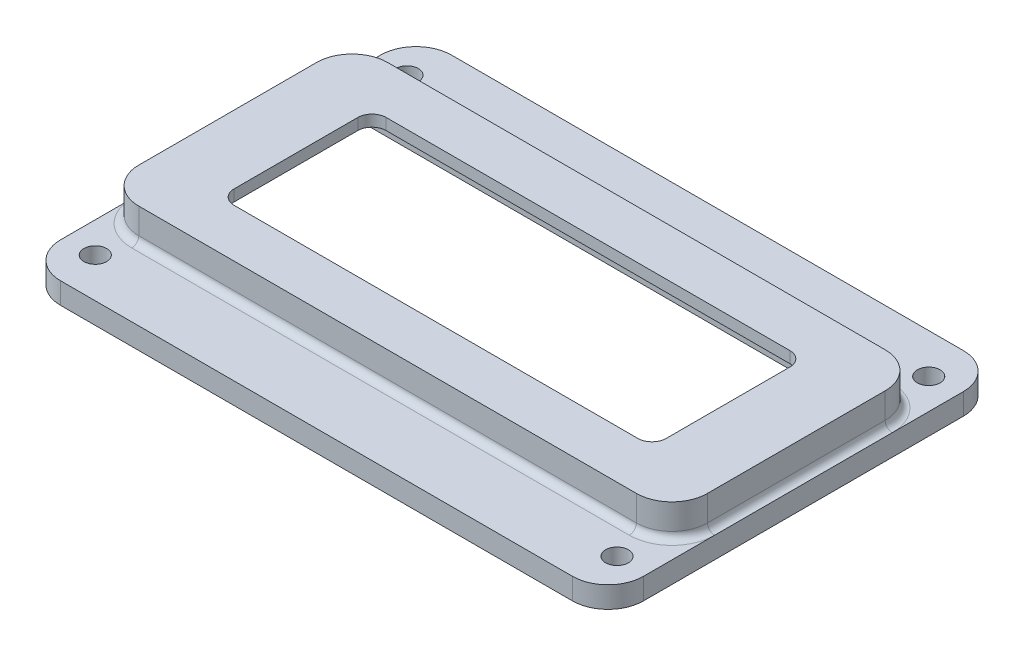
SolidWorks part; units mm, degrees
ref_plane "Front Plane" through (0, 0, 0) normal (0, 0, 1) x (1, 0, 0)
ref_plane "Top Plane" through (0, 0, 0) normal (0, 1, 0) x (1, 0, 0)
ref_plane "Right Plane" through (0, 0, 0) normal (1, 0, 0) x (0, 0, -1)
sketch "Sketch1" plane through (0, 0, 0) normal (0, 1, 0) x (1, 0, 0)
  line L1 (-52.07, 34.925) -> (52.07, 34.925)
  line L2 (-52.07, 34.925) -> (-52.07, -34.925)
  line L3 (-52.07, -34.925) -> (52.07, -34.925)
  line L4 (52.07, 34.925) -> (52.07, -34.925)
  point P4 (0, 34.925)
  point P6 (-52.07, 0)
  dimension "D1" = 69.85
  dimension "D2" = 104.14
extrude "Boss-Extrude1" add sketch "Sketch1" along normal blind 3.81
sketch "Sketch2" plane through (0, 3.81, 0) normal (0, 1, 0) x (1, 0, 0)
  line L1 (-50.8, 22.225) -> (50.8, 22.225)
  line L2 (-50.8, 22.225) -> (-50.8, -22.225)
  line L3 (-50.8, -22.225) -> (50.8, -22.225)
  line L4 (50.8, 22.225) -> (50.8, -22.225)
  line L7 (-50.8, -22.225) -> (50.8, -22.225)
  line L8 (-50.8, -22.225) -> (-50.8, 22.225)
  line L9 (-50.8, 22.225) -> (50.8, 22.225)
  line L10 (50.8, -22.225) -> (50.8, 22.225)
  point P4 (0, 22.225)
  point P5 (-50.8, 0)
  line M2 (-52.07, 34.925) -> (-52.07, -34.925)
  line M4 (52.07, -34.925) -> (52.07, 34.925)
  dimension "D1" = 44.45
  dimension "D2" = 101.6
extrude "Boss-Extrude2" add sketch "Sketch2" along normal blind 5.842 contours L3 L1 M2 M4 region at (0, 3.81, 0)
sketch "Sketch3" plane through (0, 0, 0) normal (0, -1, 0) x (1, 0, 0)
  line L1 (-50.8, 22.225) -> (50.8, 22.225)
  line L2 (-50.8, 22.225) -> (-50.8, -22.225)
  line L3 (-50.8, -22.225) -> (50.8, -22.225)
  line L4 (50.8, 22.225) -> (50.8, -22.225)
sketch "Sketch4" plane through (0, 0, 0) normal (0, -1, 0) x (1, 0, 0)
  line L1 (-48.768, 20.32) -> (48.768, 20.32)
  line L2 (-48.768, 20.32) -> (-48.768, -20.32)
  line L3 (-48.768, -20.32) -> (48.768, -20.32)
  line L4 (48.768, 20.32) -> (48.768, -20.32)
  point P4 (-48.768, 0)
  point P6 (0, 20.32)
  dimension "D1" = 40.64
  dimension "D2" = 97.536
extrude "Cut-Extrude1" cut sketch "Sketch4" against normal blind 7.62
sketch "Sketch5" plane through (0, 7.62, 0) normal (0, -1, 0) x (1, 0, 0)
  line L1 (-38.608, 13.589) -> (38.608, 13.589)
  line L2 (-38.608, 13.589) -> (-38.608, -13.589)
  line L3 (-38.608, -13.589) -> (38.608, -13.589)
  line L4 (38.608, 13.589) -> (38.608, -13.589)
  point P4 (0, 13.589)
  point P6 (-38.608, 0)
  dimension "D1" = 27.178
  dimension "D2" = 77.216
extrude "Cut-Extrude2" cut sketch "Sketch5" against normal blind 5.842
fillet "Fillet1" radius 2.54 4 edges at (38.608, 8.636, 13.589) (38.608, 8.636, -13.589) (-38.608, 8.636, 13.589) (-38.608, 8.636, -13.589)
fillet "Fillet2" radius 6.35 8 edges at (-52.07, 1.905, -34.925) (-52.07, 1.905, 34.925) (52.07, 1.905, 34.925) (52.07, 1.905, -34.925) (50.8, 6.731, -22.225) (-50.8, 6.731, -22.225) (-50.8, 6.731, 22.225) (50.8, 6.731, 22.225)
fillet "Fillet3" radius 1.27 8 edges at (48.9401, 3.81, 20.3651) (48.9401, 3.81, -20.3651) (0, 3.81, -22.225) (-48.9401, 3.81, -20.3651) (-48.9401, 3.81, 20.3651) (0, 3.81, 22.225) (50.8, 3.81, 0) (-50.8, 3.81, 0)
sketch "Sketch6" plane through (0, 3.81, 0) normal (0, 1, 0) x (1, 0, 0)
  line L0 (-5.3086, 0) -> (5.3086, 0) construction
  circle A0 centre (-46.609, 27.8447) radius 2.032
  circle A1 centre (46.609, 27.8447) radius 2.032
  circle A2 centre (46.609, -27.8447) radius 2.032
  circle A3 centre (-46.609, -27.8447) radius 2.032
  dimension "D2" = 4.064
  dimension "D1" = 93.218
  dimension "D3" = 46.609
  dimension "D4" = 27.8447
extrude "Cut-Extrude3" cut sketch "Sketch6" against normal blind 5.842
fillet "Fillet4" radius 1.27 4 edges at (48.768, 3.81, 20.32) (48.768, 3.81, -20.32) (-48.768, 3.81, 20.32) (-48.768, 3.81, -20.32)
